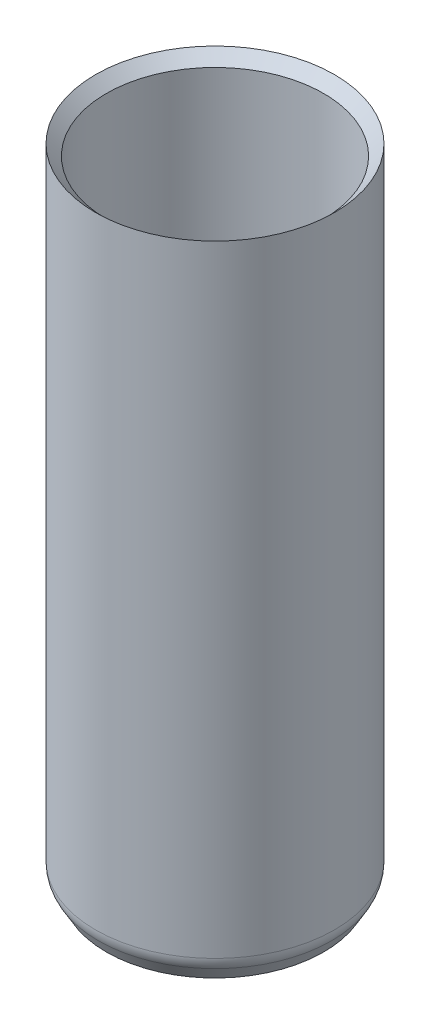
SolidWorks part; units mm, degrees
ref_plane "Front Plane" through (0, 0, 0) normal (0, 0, 1) x (1, 0, 0)
ref_plane "Top Plane" through (0, 0, 0) normal (0, 1, 0) x (1, 0, 0)
ref_plane "Right Plane" through (0, 0, 0) normal (1, 0, 0) x (0, 0, -1)
sketch "Sketch1" plane through (0, 0, 0) normal (0, 1, 0) x (1, 0, 0)
  circle A0 centre (0, 0) radius 27.5
  circle A1 centre (0, 0) radius 25
  dimension "D1" = 55
  dimension "D2" = 50
extrude "Boss-Extrude1" add sketch "Sketch1" along normal blind 150
chamfer "Chamfer2" distance 3 angle 45 1 edges at (0, 150, 25)
chamfer "Chamfer4" distance 3 angle 60 1 edges at (0, 0, 27.5) first distance on face at (0, 0, 27.5)
fillet "Fillet1" radius 5 1 edges at (0, 5.1962, 27.5)
